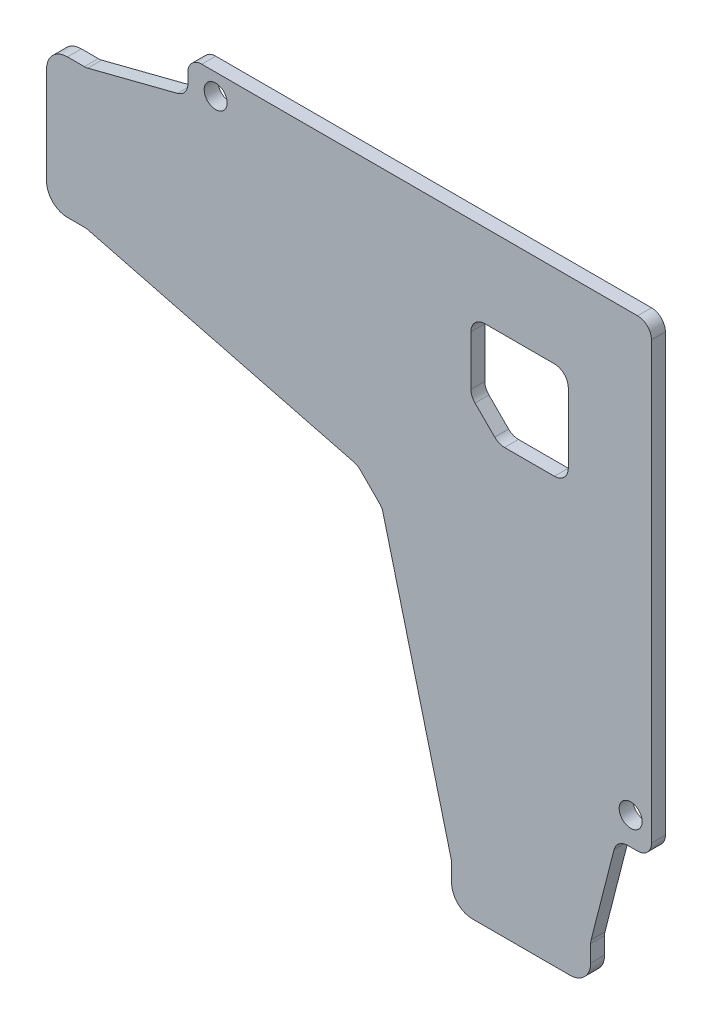
SolidWorks part; units mm, degrees
ref_plane "Front Plane" through (0, 0, 0) normal (0, 0, 1) x (1, 0, 0)
ref_plane "Top Plane" through (0, 0, 0) normal (0, 1, 0) x (1, 0, 0)
ref_plane "Right Plane" through (0, 0, 0) normal (1, 0, 0) x (0, 0, -1)
sketch "Sketch1" plane through (0, 0, 0) normal (0, 0, 1) x (1, 0, 0)
  line L0 (-86, -7.75) -> (-86, -27.75)
  line L1 (-27.75, -86) -> (-7.75, -86)
  line L2 (-86, -7.75) -> (-95.5, -7.75) construction
  line L3 (-86, -27.75) -> (-80.5674, -27.75)
  line L4 (-27.75, -86) -> (-27.75, -95.5) construction
  line L5 (-7.75, -86) -> (-7.75, -80.5674)
  line L23 (-10.25, -92) -> (-10.25, -95.5)
  line L24 (-10.25, -95.5) -> (-7.75, -95.5)
  line L25 (-7.75, -95.5) -> (-7.75, -80.5674)
  line L26 (-7.6874, -80.0709) -> (-4.3853, -67.1846)
  line L27 (-2.4479, -65.6811) -> (-1, -65.6811)
  line L28 (1, -63.6811) -> (1, -1)
  line L29 (-1, 1) -> (-63.6811, 1)
  line L30 (-65.6811, -1) -> (-65.6811, -2.4479)
  line L31 (-67.1846, -4.3853) -> (-80.0709, -7.6874)
  line L32 (-80.5674, -7.75) -> (-95.5, -7.75)
  line L33 (-95.5, -7.75) -> (-95.5, -10.25)
  line L34 (-95.5, -10.25) -> (-92, -10.25)
  line L35 (-90, -12.25) -> (-90, -23.25)
  line L36 (-92, -25.25) -> (-95.5, -25.25)
  line L37 (-95.5, -25.25) -> (-95.5, -27.75)
  line L38 (-95.5, -27.75) -> (-80.5674, -27.75)
  line L39 (-80.0709, -27.8126) -> (-41.8142, -37.6159)
  line L40 (-40.8965, -38.1391) -> (-38.1391, -40.8965)
  line L41 (-37.6159, -41.8142) -> (-27.8126, -80.0709)
  line L42 (-27.75, -80.5674) -> (-27.75, -95.5)
  line L43 (-27.75, -95.5) -> (-25.25, -95.5)
  line L44 (-25.25, -95.5) -> (-25.25, -92)
  line L45 (-23.25, -90) -> (-12.25, -90)
  line L46 (-10.25, -92) -> (-10.25, -95.5) construction
  line L47 (-10.25, -95.5) -> (-7.75, -95.5) construction
  line L48 (-7.75, -95.5) -> (-7.75, -86) construction
  line L49 (-7.6874, -80.0709) -> (-4.3853, -67.1846)
  line L50 (-2.4479, -65.6811) -> (-1, -65.6811)
  line L51 (1, -63.6811) -> (1, -1)
  line L52 (-1, 1) -> (-63.6811, 1)
  line L53 (-65.6811, -1) -> (-65.6811, -2.4479)
  line L54 (-67.1846, -4.3853) -> (-80.0709, -7.6874)
  line L55 (-80.5674, -7.75) -> (-86, -7.75)
  line L56 (-95.5, -7.75) -> (-95.5, -10.25) construction
  line L57 (-95.5, -10.25) -> (-92, -10.25) construction
  line L58 (-90, -12.25) -> (-90, -23.25) construction
  line L59 (-92, -25.25) -> (-95.5, -25.25) construction
  line L60 (-95.5, -25.25) -> (-95.5, -27.75) construction
  line L61 (-95.5, -27.75) -> (-86, -27.75) construction
  line L62 (-80.0709, -27.8126) -> (-41.8142, -37.6159)
  line L63 (-40.8965, -38.1391) -> (-38.1391, -40.8965)
  line L64 (-37.6159, -41.8142) -> (-27.8126, -80.0709)
  line L65 (-27.75, -80.5674) -> (-27.75, -86)
  line L66 (-27.75, -95.5) -> (-25.25, -95.5) construction
  line L67 (-25.25, -95.5) -> (-25.25, -92) construction
  line L68 (-23.25, -90) -> (-12.25, -90) construction
  arc A15 (-7.6874, -80.0709) -> (-7.75, -80.5674) centre (-5.75, -80.5674) ccw
  arc A16 (-2.4479, -65.6811) -> (-4.3853, -67.1846) centre (-2.4479, -67.6811) ccw
  arc A17 (-1, -65.6811) -> (1, -63.6811) centre (-1, -63.6811) ccw
  arc A18 (1, -1) -> (-1, 1) centre (-1, -1) ccw
  arc A19 (-63.6811, 1) -> (-65.6811, -1) centre (-63.6811, -1) ccw
  arc A20 (-67.1846, -4.3853) -> (-65.6811, -2.4479) centre (-67.6811, -2.4479) ccw
  arc A21 (-80.5674, -7.75) -> (-80.0709, -7.6874) centre (-80.5674, -5.75) ccw
  arc A22 (-90, -12.25) -> (-92, -10.25) centre (-92, -12.25) ccw
  arc A23 (-92, -25.25) -> (-90, -23.25) centre (-92, -23.25) ccw
  arc A24 (-80.0709, -27.8126) -> (-80.5674, -27.75) centre (-80.5674, -29.75) ccw
  arc A25 (-40.8965, -38.1391) -> (-41.8142, -37.6159) centre (-42.3107, -39.5533) ccw
  arc A26 (-37.6159, -41.8142) -> (-38.1391, -40.8965) centre (-39.5533, -42.3107) ccw
  arc A27 (-27.75, -80.5674) -> (-27.8126, -80.0709) centre (-29.75, -80.5674) ccw
  arc A28 (-23.25, -90) -> (-25.25, -92) centre (-23.25, -92) ccw
  arc A29 (-10.25, -92) -> (-12.25, -90) centre (-12.25, -92) ccw
  arc A30 (-7.6874, -80.0709) -> (-7.75, -80.5674) centre (-5.75, -80.5674) ccw
  arc A31 (-2.4479, -65.6811) -> (-4.3853, -67.1846) centre (-2.4479, -67.6811) ccw
  arc A32 (-1, -65.6811) -> (1, -63.6811) centre (-1, -63.6811) ccw
  arc A33 (1, -1) -> (-1, 1) centre (-1, -1) ccw
  arc A34 (-63.6811, 1) -> (-65.6811, -1) centre (-63.6811, -1) ccw
  arc A35 (-67.1846, -4.3853) -> (-65.6811, -2.4479) centre (-67.6811, -2.4479) ccw
  arc A36 (-80.5674, -7.75) -> (-80.0709, -7.6874) centre (-80.5674, -5.75) ccw
  arc A37 (-90, -12.25) -> (-92, -10.25) centre (-92, -12.25) ccw construction
  arc A38 (-92, -25.25) -> (-90, -23.25) centre (-92, -23.25) ccw construction
  arc A39 (-80.0709, -27.8126) -> (-80.5674, -27.75) centre (-80.5674, -29.75) ccw
  arc A40 (-40.8965, -38.1391) -> (-41.8142, -37.6159) centre (-42.3107, -39.5533) ccw
  arc A41 (-37.6159, -41.8142) -> (-38.1391, -40.8965) centre (-39.5533, -42.3107) ccw
  arc A42 (-27.75, -80.5674) -> (-27.8126, -80.0709) centre (-29.75, -80.5674) ccw
  arc A43 (-23.25, -90) -> (-25.25, -92) centre (-23.25, -92) ccw construction
  arc A44 (-10.25, -92) -> (-12.25, -90) centre (-12.25, -92) ccw construction
  dimension "D2" = 4
  dimension "D3" = 4
  dimension "D1" = 0
sketch "Sketch2" plane through (0, 0, 0) normal (0, 0, 1) x (1, 0, 0)
  circle A0 centre (-61.6811, -2) radius 1.65 construction
  circle A1 centre (-2, -61.6811) radius 1.65 construction
  circle A2 centre (-61.6811, -2) radius 1.65
  circle A3 centre (-2, -61.6811) radius 1.65
sketch "Sketch4" plane through (0, 0, 0) normal (0, 0, 1) x (1, 0, 0)
  line L0 (-24.9687, -12.9687) -> (-24.9687, -20.1403) construction
  line L1 (-12.9687, -10.9687) -> (-22.9687, -10.9687) construction
  line L2 (-10.9687, -22.9687) -> (-10.9687, -12.9687) construction
  line L3 (-20.1403, -24.9687) -> (-12.9687, -24.9687) construction
  line L4 (-24.9687, -12.9687) -> (-24.9687, -20.1403)
  line L5 (-12.9687, -10.9687) -> (-22.9687, -10.9687)
  line L6 (-10.9687, -22.9687) -> (-10.9687, -12.9687)
  line L7 (-20.1403, -24.9687) -> (-12.9687, -24.9687)
  line L8 (-21.5545, -24.3829) -> (-24.3829, -21.5545) construction
  line L9 (-21.5545, -24.3829) -> (-24.3829, -21.5545)
  arc A0 (-24.9687, -20.1403) -> (-24.3829, -21.5545) centre (-22.9687, -20.1403) ccw construction
  arc A1 (-21.5545, -24.3829) -> (-20.1403, -24.9687) centre (-20.1403, -22.9687) ccw construction
  arc A2 (-22.9687, -10.9687) -> (-24.9687, -12.9687) centre (-22.9687, -12.9687) ccw construction
  arc A3 (-10.9687, -12.9687) -> (-12.9687, -10.9687) centre (-12.9687, -12.9687) ccw construction
  arc A4 (-12.9687, -24.9687) -> (-10.9687, -22.9687) centre (-12.9687, -22.9687) ccw construction
  arc A5 (-24.9687, -20.1403) -> (-24.3829, -21.5545) centre (-22.9687, -20.1403) ccw
  arc A6 (-22.9687, -10.9687) -> (-24.9687, -12.9687) centre (-22.9687, -12.9687) ccw
  arc A7 (-10.9687, -12.9687) -> (-12.9687, -10.9687) centre (-12.9687, -12.9687) ccw
  arc A8 (-12.9687, -24.9687) -> (-10.9687, -22.9687) centre (-12.9687, -22.9687) ccw
  arc A9 (-21.5545, -24.3829) -> (-20.1403, -24.9687) centre (-20.1403, -22.9687) ccw
extrude "Boss-Extrude1" add sketch "Sketch1" along normal blind 2
extrude "Cut-Extrude2" cut sketch "Sketch4" along normal through all
sketch "Sketch5" plane through (0, 0, 0) normal (0, 0, 1) x (1, 0, 0)
  line L0 (-78.4965, -9.8647) -> (-46.0979, -1.5626) construction
  line L1 (-78.4965, -9.8647) -> (-46.0979, -1.5626) construction
  line L2 (-80, -11.8021) -> (-80, -23.6979) construction
  line L3 (-40.5305, -35.3641) -> (-78.4965, -25.6353) construction
  line L4 (-35.8872, -39.6128) -> (-39.6128, -35.8872) construction
  line L5 (-25.6353, -78.4965) -> (-35.3641, -40.5305) construction
  line L6 (-23.6979, -80) -> (-11.8021, -80) construction
  line L7 (-1.5626, -46.0979) -> (-9.8647, -78.4965) construction
  line L8 (-1.5, -3.5) -> (-1.5, -45.6015) construction
  line L9 (-45.6015, -1.5) -> (-3.5, -1.5) construction
  line L10 (-80, -11.8021) -> (-80, -23.6979) construction
  line L11 (-40.5305, -35.3641) -> (-78.4965, -25.6353) construction
  line L12 (-35.8872, -39.6128) -> (-39.6128, -35.8872) construction
  line L13 (-25.6353, -78.4965) -> (-35.3641, -40.5305) construction
  line L14 (-23.6979, -80) -> (-11.8021, -80) construction
  line L15 (-1.5626, -46.0979) -> (-9.8647, -78.4965) construction
  line L16 (-1.5, -3.5) -> (-1.5, -45.6015) construction
  line L17 (-45.6015, -1.5) -> (-3.5, -1.5) construction
  line L18 (-78.422, -10.1553) -> (-46.0235, -1.8532)
  line L19 (-45.6015, -1.8) -> (-3.5, -1.8)
  line L20 (-1.8, -3.5) -> (-1.8, -45.6015)
  line L21 (-1.8532, -46.0235) -> (-10.1553, -78.422)
  line L22 (-23.6979, -79.7) -> (-11.8021, -79.7)
  line L23 (-25.3447, -78.422) -> (-35.0734, -40.456)
  line L24 (-35.6751, -39.4006) -> (-39.4006, -35.6751)
  line L25 (-40.456, -35.0734) -> (-78.422, -25.3447)
  line L26 (-79.7, -11.8021) -> (-79.7, -23.6979)
  line L27 (-77.8, -11.9573) -> (-77.8, -23.5427)
  line L28 (-39.9844, -33.2329) -> (-77.8, -23.5427)
  line L29 (-34.3316, -38.0571) -> (-38.0571, -34.3316)
  line L30 (-23.5427, -77.8) -> (-33.2329, -39.9844)
  line L31 (-23.5427, -77.8) -> (-11.9573, -77.8)
  line L32 (-3.7, -45.5763) -> (-11.9573, -77.8)
  line L33 (-3.7, -3.7) -> (-3.7, -45.5763)
  line L34 (-45.5763, -3.7) -> (-3.7, -3.7)
  line L35 (-77.8, -11.9573) -> (-45.5763, -3.7)
  arc A0 (-78.4965, -9.8647) -> (-80, -11.8021) centre (-78, -11.8021) ccw construction
  arc A1 (-80, -23.6979) -> (-78.4965, -25.6353) centre (-78, -23.6979) ccw construction
  arc A2 (-39.6128, -35.8872) -> (-40.5305, -35.3641) centre (-41.027, -37.3015) ccw construction
  arc A3 (-25.6353, -78.4965) -> (-23.6979, -80) centre (-23.6979, -78) ccw construction
  arc A4 (-11.8021, -80) -> (-9.8647, -78.4965) centre (-11.8021, -78) ccw construction
  arc A5 (-1.5626, -46.0979) -> (-1.5, -45.6015) centre (-3.5, -45.6015) ccw construction
  arc A6 (-1.5, -3.5) -> (-3.5, -1.5) centre (-3.5, -3.5) ccw construction
  arc A7 (-45.6015, -1.5) -> (-46.0979, -1.5626) centre (-45.6015, -3.5) ccw construction
  arc A8 (-78.4965, -9.8647) -> (-80, -11.8021) centre (-78, -11.8021) ccw construction
  arc A9 (-80, -23.6979) -> (-78.4965, -25.6353) centre (-78, -23.6979) ccw construction
  arc A10 (-39.6128, -35.8872) -> (-40.5305, -35.3641) centre (-41.027, -37.3015) ccw construction
  arc A11 (-25.6353, -78.4965) -> (-23.6979, -80) centre (-23.6979, -78) ccw construction
  arc A12 (-11.8021, -80) -> (-9.8647, -78.4965) centre (-11.8021, -78) ccw construction
  arc A13 (-1.5626, -46.0979) -> (-1.5, -45.6015) centre (-3.5, -45.6015) ccw construction
  arc A14 (-1.5, -3.5) -> (-3.5, -1.5) centre (-3.5, -3.5) ccw construction
  arc A15 (-45.6015, -1.5) -> (-46.0979, -1.5626) centre (-45.6015, -3.5) ccw construction
  arc A16 (-45.6015, -1.8) -> (-46.0235, -1.8532) centre (-45.6015, -3.5) ccw
  arc A17 (-1.8, -3.5) -> (-3.5, -1.8) centre (-3.5, -3.5) ccw
  arc A18 (-1.8532, -46.0235) -> (-1.8, -45.6015) centre (-3.5, -45.6015) ccw
  arc A19 (-11.8021, -79.7) -> (-10.1553, -78.422) centre (-11.8021, -78) ccw
  arc A20 (-25.3447, -78.422) -> (-23.6979, -79.7) centre (-23.6979, -78) ccw
  arc A21 (-35.0734, -40.456) -> (-35.6751, -39.4006) centre (-37.3015, -41.027) ccw
  arc A22 (-39.4006, -35.6751) -> (-40.456, -35.0734) centre (-41.027, -37.3015) ccw
  arc A23 (-79.7, -23.6979) -> (-78.422, -25.3447) centre (-78, -23.6979) ccw
  arc A24 (-35.3641, -40.5305) -> (-35.8872, -39.6128) centre (-37.3015, -41.027) ccw construction
  arc A25 (-35.3641, -40.5305) -> (-35.8872, -39.6128) centre (-37.3015, -41.027) ccw construction
  arc A26 (-78.422, -10.1553) -> (-79.7, -11.8021) centre (-78, -11.8021) ccw
  arc A27 (-77.8, -23.5427) -> (-77.8, -23.5427) centre (-77.8, -23.5427) ccw
  arc A28 (-38.0571, -34.3316) -> (-39.9844, -33.2329) centre (-41.027, -37.3015) ccw
  arc A29 (-33.2329, -39.9844) -> (-34.3316, -38.0571) centre (-37.3015, -41.027) ccw
  arc A30 (-23.5427, -77.8) -> (-23.5427, -77.8) centre (-23.5427, -77.8) ccw
  arc A31 (-11.9573, -77.8) -> (-11.9573, -77.8) centre (-11.9573, -77.8) ccw
  arc A32 (-3.7, -45.5763) -> (-3.7, -45.5763) centre (-3.7, -45.5763) ccw
  arc A33 (-3.7, -3.7) -> (-3.7, -3.7) centre (-3.7, -3.7) ccw
  arc A34 (-45.5763, -3.7) -> (-45.5763, -3.7) centre (-45.5763, -3.7) ccw
  arc A35 (-77.8, -11.9573) -> (-77.8, -11.9573) centre (-77.8, -11.9573) ccw
  dimension "D1" = 0.3
  dimension "D2" = 2.2
extrude "Boss-Extrude2" add sketch "Sketch5" against normal blind 1.2
chamfer "Chamfer1" distance 1.2 angle 45 11 edges at (-28.3878, -58.8922, 0) (-33.6527, -38.9469, 0) (-36.1944, -36.1944, 0) (-38.9469, -33.6527, 0) (-17.75, -77.8, 0) (-7.8287, -61.6881, 0) (-3.7, -24.6381, 0) (-24.6381, -3.7, 0) (-61.6881, -7.8287, 0) (-77.8, -17.75, 0) (-58.8922, -28.3878, 0)
extrude "Cut-Extrude3" cut sketch "Sketch2" along normal through all
fillet "Fillet1" radius 3 4 edges at (-27.75, -86, 1) (-7.75, -86, 1) (-86, -7.75, 1) (-86, -27.75, 1)
